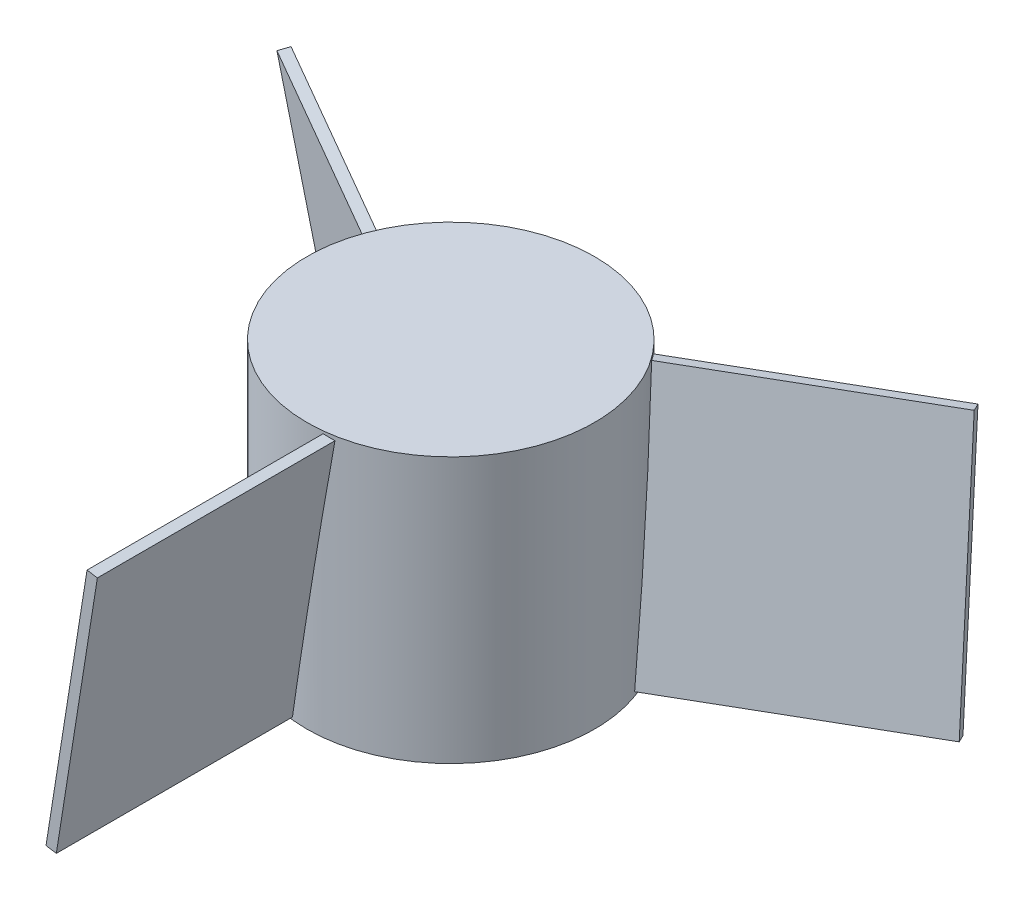
SolidWorks part; units mm, degrees
ref_plane "Front Plane" through (0, 0, 0) normal (0, 0, 1) x (1, 0, 0)
ref_plane "Top Plane" through (0, 0, 0) normal (0, 1, 0) x (1, 0, 0)
ref_plane "Right Plane" through (0, 0, 0) normal (1, 0, 0) x (0, 0, -1)
sketch "Sketch1" plane through (0, 0, 0) normal (0, 1, 0) x (1, 0, 0)
  circle A0 centre (0, 0) radius 82.5
  dimension "D1" = 165
extrude "Boss-Extrude1" add sketch "Sketch1" along normal blind 152.4
sketch "Sketch2" plane through (0, 0, 0) normal (1, 0, 0) x (0, 0, -1)
  line L0 (-135.2989, 76.2) -> (106.0289, 76.2) construction
  line L1 (-82.5, 0) -> (82.5, 0) construction
  line L2 (82.5, 152.4) -> (-82.5, 152.4) construction
ref_plane "Plane1" through (-11.7735, 1.8647, 0) normal (0.9877, -0.1564, 0) x (0, 0, -1)
ref_axis "Axis1" through (0, 152.4, 0) along (0, -1, 0)
sketch "Sketch3" plane through (-11.7735, 1.8647, 0) normal (0.9877, -0.1564, 0) x (0, 0, -1)
  line L1 (0, 0) -> (-217.5, 0)
  line L2 (0, 0) -> (0, 150.5237)
  line L3 (0, 150.5237) -> (-217.5, 150.5237)
  line L4 (-217.5, 0) -> (-217.5, 150.5237)
  line L5 (0, 150.5237) -> (0, 0) construction
  dimension "D1" = 217.5
extrude "Boss-Extrude2" add sketch "Sketch3" along normal mid plane 6
pattern_circular "CirPattern1" count 3 over 360 about axis through (0, 152.4, 0) along (0, -1, 0) of "Boss-Extrude2"
